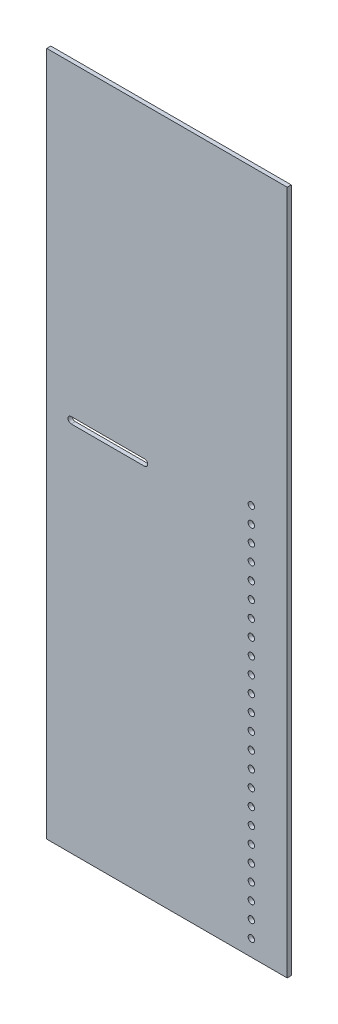
SolidWorks part; units mm, degrees
ref_plane "Front Plane" through (0, 0, 0) normal (1, 0, 0) x (0, 1, 0)
ref_plane "Top Plane" through (0, 0, 0) normal (0, 0, 1) x (0, 1, 0)
ref_plane "Right Plane" through (0, 0, 0) normal (0, 1, 0) x (-1, 0, 0)
sketch "Sketch1" plane through (0, 0, 0) normal (0, 0, 1) x (0, 1, 0)
  line L1 (-266.7, -93.6625) -> (266.7, -93.6625)
  line L2 (-266.7, -93.6625) -> (-266.7, 93.6625)
  line L3 (-266.7, 93.6625) -> (266.7, 93.6625)
  line L4 (266.7, -93.6625) -> (266.7, 93.6625)
  line L5 (-266.7, -93.6625) -> (266.7, 93.6625) construction
  line L6 (-266.7, 93.6625) -> (266.7, -93.6625) construction
  point P0 (0, 0)
  dimension "D1" = 533.4
  dimension "D2" = 187.325
extrude "Boss-Extrude1" add sketch "Sketch1" along normal blind 3.175
sketch "Sketch2" plane through (0, 0, 3.175) normal (0, 0, 1) x (1, 0, 0)
  line L0 (-93.6625, 266.7) -> (-93.6625, -266.7) construction
  line L1 (-93.6625, -266.7) -> (93.6625, -266.7) construction
  line L2 (-74.6125, 22.9108) -> (-17.4625, 22.9108)
  line L3 (-17.4625, 27.8892) -> (-74.6125, 27.8892)
  circle A0 centre (-74.6125, 25.4) radius 2.4892 construction
  circle A1 centre (-17.4625, 25.4) radius 2.4892 construction
  arc A2 (-74.6125, 22.9108) -> (-74.6125, 27.8892) centre (-74.6125, 25.4) cw
  arc A3 (-17.4625, 22.9108) -> (-17.4625, 27.8892) centre (-17.4625, 25.4) ccw
  point P0 (-17.4625, 25.4)
  point P1 (-74.6125, 25.4)
  dimension "D4" = 4.9784
  dimension "D1" = 57.15
  dimension "D2" = 19.05
  dimension "D3" = 292.1
extrude "Cut-Extrude1" cut sketch "Sketch2" against normal through all
sketch "Sketch3" plane through (0, 0, 3.175) normal (0, 0, 1) x (1, 0, 0)
  line L0 (93.6625, -266.7) -> (93.6625, 266.7) construction
  line L1 (-93.6625, -266.7) -> (93.6625, -266.7) construction
  point P0 (65.7225, -254)
  point P3 (65.7225, -241.3)
  point P4 (65.7225, -228.6)
  point P5 (65.7225, -215.9)
  point P6 (65.7225, -203.2)
  point P7 (65.7225, -190.5)
  point P8 (65.7225, -177.8)
  point P9 (65.7225, -165.1)
  point P10 (65.7225, -152.4)
  point P11 (65.7225, -139.7)
  point P12 (65.7225, -127)
  point P13 (65.7225, -114.3)
  point P14 (65.7225, -101.6)
  point P15 (65.7225, -88.9)
  point P16 (65.7225, -76.2)
  point P17 (65.7225, -63.5)
  point P18 (65.7225, -50.8)
  point P19 (65.7225, -38.1)
  point P20 (65.7225, -25.4)
  point P21 (65.7225, -12.7)
  point P22 (65.7225, 0)
  point P23 (65.7225, 12.7)
  point P24 (65.7225, 25.4)
  point P25 (65.7225, 38.1)
  dimension "D2" = 27.94
  dimension "D3" = 12.7
  dimension "D4" = 12.7
  dimension "D1" = 24
hole_wizard "#9 (0.196) Diameter Hole1" positions "Sketch3" profile "Sketch4" hole size "#9" standard "ANSI Inch" end condition through all
sketch "Sketch4" plane through (65.7225, -254, 3.175) normal (1, 0, 0) x (0, -1, 0)
  line L0 (0, 0) -> (0, 3.175)
  line L1 (0, 3.175) -> (2.4892, 3.175)
  line L2 (2.4892, 3.175) -> (2.4892, 0)
  line L5 (2.4892, 0) -> (0, 0)
  line L11 (0, -6.35) -> (0, 107.95) construction
  dimension "Thru Hole Dia." = 4.9784
  dimension "Thru Hole Depth" = 3.175
